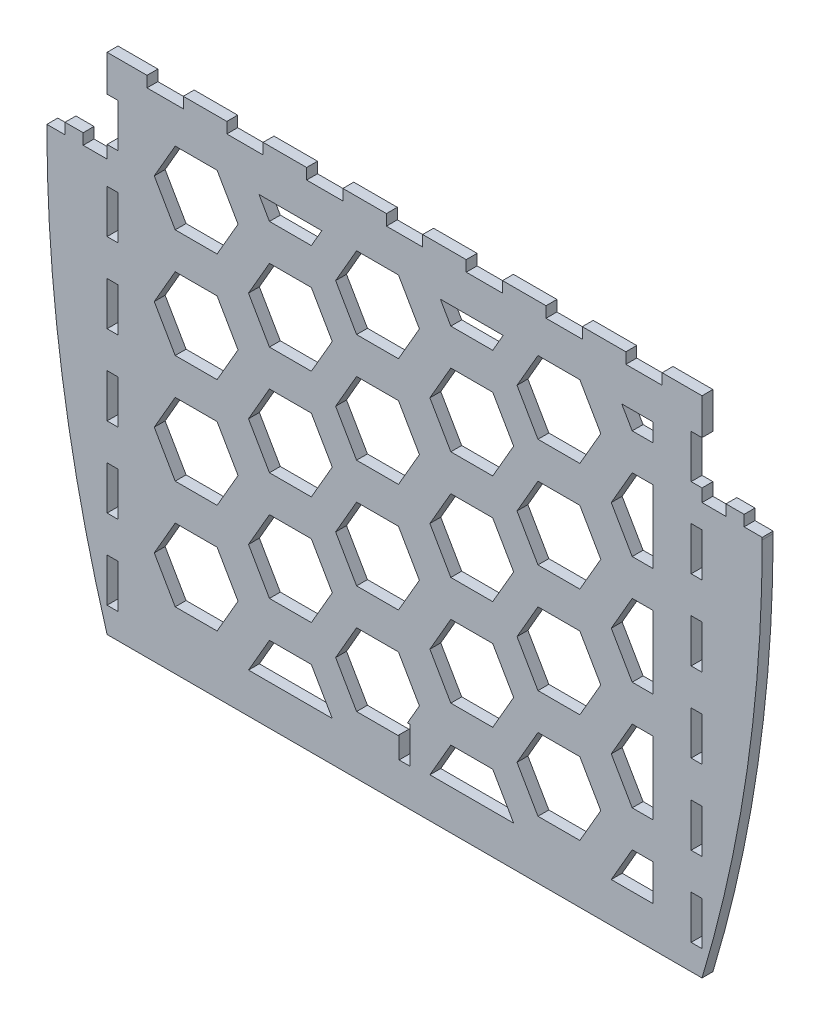
SolidWorks part; units mm, degrees
material "birch 3mm plywood"
ref_plane "Front Plane" through (0, 0, 0) normal (0, 0, 1) x (1, 0, 0)
ref_plane "Top Plane" through (0, 0, 0) normal (0, 1, 0) x (1, 0, 0)
ref_plane "Right Plane" through (0, 0, 0) normal (1, 0, 0) x (0, 0, -1)
sketch "Sketch1" plane through (0, 0, 152) normal (0, 0, 1) x (1, 0, 0)
  line L1 (-82, 69.5) -> (82, 69.5)
  line L2 (-82, 69.5) -> (-82, 44)
  line L3 (-82, -69.5) -> (82, -69.5)
  line L4 (82, 69.5) -> (82, 44)
  line L8 (-88.6, 47) -> (-93.6, 47)
  line L9 (-98.6, 44) -> (-98.6, 43.3771)
  line L12 (75, -62.5) -> (-75, -62.5) construction
  line L13 (75, 62.5) -> (75, -62.5) construction
  line L14 (-75, -62.5) -> (-75, 62.5) construction
  line L15 (-75, 62.5) -> (75, 62.5) construction
  line L33 (-93.6, 47) -> (-93.6, 44)
  line L34 (-93.6, 44) -> (-98.6, 44)
  line L35 (-88.6, 47) -> (-88.6, 44)
  line L36 (-88.6, 44) -> (-82, 44)
  line L37 (98.6, 44) -> (98.6, 43.3771)
  line L38 (93.6, 44) -> (98.6, 44)
  line L39 (93.6, 47) -> (93.6, 44)
  line L40 (88.6, 47) -> (93.6, 47)
  line L41 (88.6, 47) -> (88.6, 44)
  line L42 (88.6, 44) -> (82, 44)
  arc A12 (-98.6, 43.3771) -> (-82, -69.5) centre (293.4723, 43.3771) ccw
  arc A14 (98.6, 43.3771) -> (82, -69.5) centre (-293.4723, 43.3771) cw
  dimension "D3" = 7
  dimension "D11" = 150
  dimension "D12" = 125
  dimension "D13" = 7
  dimension "D14" = 22.5
  dimension "D15" = 16.6
  dimension "D16" = 3
  dimension "D17" = 5
  dimension "D18" = 5
extrude "Boss-Extrude1" add sketch "Sketch1" along normal blind 3
sketch "Sketch2" plane through (0, 0, 155) normal (0, 0, 1) x (1, 0, 0)
  line L0 (0, 69.5) -> (0, -69.5) construction
  line L1 (17, 69.5) -> (17, 66.5)
  line L2 (-5, 69.5) -> (5, 69.5)
  line L3 (-5, 69.5) -> (-5, 66.5)
  line L4 (-82, 69.5) -> (-82, 44)
  line L5 (-82, -69.5) -> (82, -69.5)
  line L6 (82, 44) -> (82, 69.5)
  line L7 (82, 69.5) -> (-82, 69.5)
  line L8 (-82, 69.5) -> (-82, 44)
  line L9 (-82, -69.5) -> (82, -69.5)
  line L10 (82, 44) -> (82, 69.5)
  line L11 (82, 69.5) -> (-82, 69.5)
  line L12 (-5, 66.5) -> (5, 66.5)
  line L13 (5, 69.5) -> (5, 66.5)
  line L14 (17, 69.5) -> (27, 69.5)
  line L15 (27, 69.5) -> (27, 66.5)
  line L16 (17, 66.5) -> (27, 66.5)
  line L17 (39, 69.5) -> (39, 66.5)
  line L18 (39, 69.5) -> (49, 69.5)
  line L19 (49, 69.5) -> (49, 66.5)
  line L20 (39, 66.5) -> (49, 66.5)
  line L21 (61, 69.5) -> (61, 66.5)
  line L22 (61, 69.5) -> (71, 69.5)
  line L23 (71, 69.5) -> (71, 66.5)
  line L24 (61, 66.5) -> (71, 66.5)
  line L25 (-27, 69.5) -> (-27, 66.5)
  line L26 (-27, 69.5) -> (-17, 69.5)
  line L27 (-17, 69.5) -> (-17, 66.5)
  line L28 (-27, 66.5) -> (-17, 66.5)
  line L29 (-49, 69.5) -> (-49, 66.5)
  line L30 (-49, 69.5) -> (-39, 69.5)
  line L31 (-39, 69.5) -> (-39, 66.5)
  line L32 (-49, 66.5) -> (-39, 66.5)
  line L33 (-71, 69.5) -> (-71, 66.5)
  line L34 (-71, 69.5) -> (-61, 69.5)
  line L35 (-61, 69.5) -> (-61, 66.5)
  line L36 (-71, 66.5) -> (-61, 66.5)
  line L37 (-82, 37.5) -> (-82, 25.5)
  line L38 (-82, 59.5) -> (-79, 59.5)
  line L39 (-82, 59.5) -> (-82, 47.5)
  line L40 (-82, 47.5) -> (-79, 47.5)
  line L41 (-79, 59.5) -> (-79, 47.5)
  line L42 (-82, 37.5) -> (-79, 37.5)
  line L43 (-79, 37.5) -> (-79, 25.5)
  line L44 (-82, 25.5) -> (-79, 25.5)
  line L45 (-82, 15.5) -> (-82, 3.5)
  line L46 (-82, 15.5) -> (-79, 15.5)
  line L47 (-79, 15.5) -> (-79, 3.5)
  line L48 (-82, 3.5) -> (-79, 3.5)
  line L49 (-82, -6.5) -> (-82, -18.5)
  line L50 (-82, -6.5) -> (-79, -6.5)
  line L51 (-79, -6.5) -> (-79, -18.5)
  line L52 (-82, -18.5) -> (-79, -18.5)
  line L53 (-82, -28.5) -> (-82, -40.5)
  line L54 (-82, -28.5) -> (-79, -28.5)
  line L55 (-79, -28.5) -> (-79, -40.5)
  line L56 (-82, -40.5) -> (-79, -40.5)
  line L57 (-82, -50.5) -> (-82, -62.5)
  line L58 (-82, -50.5) -> (-79, -50.5)
  line L59 (-79, -50.5) -> (-79, -62.5)
  line L60 (-82, -62.5) -> (-79, -62.5)
  line L65 (82, -50.5) -> (79, -50.5)
  line L66 (79, -50.5) -> (79, -62.5)
  line L67 (82, -62.5) -> (79, -62.5)
  line L68 (82, -50.5) -> (82, -62.5)
  line L69 (82, -28.5) -> (79, -28.5)
  line L70 (79, -28.5) -> (79, -40.5)
  line L71 (82, -40.5) -> (79, -40.5)
  line L72 (82, -28.5) -> (82, -40.5)
  line L73 (82, -6.5) -> (79, -6.5)
  line L74 (79, -6.5) -> (79, -18.5)
  line L75 (82, -18.5) -> (79, -18.5)
  line L76 (82, -6.5) -> (82, -18.5)
  line L77 (82, 15.5) -> (79, 15.5)
  line L78 (79, 15.5) -> (79, 3.5)
  line L79 (82, 3.5) -> (79, 3.5)
  line L80 (82, 15.5) -> (82, 3.5)
  line L81 (82, 37.5) -> (79, 37.5)
  line L82 (79, 37.5) -> (79, 25.5)
  line L83 (82, 25.5) -> (79, 25.5)
  line L84 (82, 37.5) -> (82, 25.5)
  line L85 (82, 47.5) -> (79, 47.5)
  line L86 (79, 59.5) -> (79, 47.5)
  line L87 (82, 59.5) -> (79, 59.5)
  line L88 (82, 59.5) -> (82, 47.5)
  line L97 (-88.6, 47) -> (-93.6, 47)
  line L98 (-88.6, 47) -> (-93.6, 47)
  line L99 (-98.6, 44) -> (-98.6, 43.3771)
  line L100 (-98.6, 44) -> (-98.6, 43.3771)
  line L101 (98.6, 43.3771) -> (98.6, 44)
  line L103 (98.6, 43.3771) -> (98.6, 44)
  line L109 (-82, 44) -> (-88.6, 44)
  line L110 (-82, 44) -> (-88.6, 44)
  line L111 (-88.6, 44) -> (-88.6, 47)
  line L112 (-88.6, 44) -> (-88.6, 47)
  line L113 (-93.6, 47) -> (-93.6, 44)
  line L114 (-93.6, 47) -> (-93.6, 44)
  line L115 (-93.6, 44) -> (-98.6, 44)
  line L116 (-93.6, 44) -> (-98.6, 44)
  line L121 (98.6, 44) -> (93.6, 44)
  line L122 (98.6, 44) -> (93.6, 44)
  line L123 (93.6, 44) -> (93.6, 47)
  line L124 (93.6, 44) -> (93.6, 47)
  line L125 (93.6, 47) -> (88.6, 47)
  line L126 (93.6, 47) -> (88.6, 47)
  line L127 (88.6, 47) -> (88.6, 44)
  line L128 (88.6, 47) -> (88.6, 44)
  line L129 (88.6, 44) -> (82, 44)
  line L130 (88.6, 44) -> (82, 44)
  arc A2 (-98.6, 43.3771) -> (-82, -69.5) centre (293.4723, 43.3771) ccw
  arc A3 (-98.6, 43.3771) -> (-82, -69.5) centre (293.4723, 43.3771) ccw
  arc A4 (82, -69.5) -> (98.6, 43.3771) centre (-293.4723, 43.3771) ccw
  arc A6 (82, -69.5) -> (98.6, 43.3771) centre (-293.4723, 43.3771) ccw
  point P10 (0, 66.5)
  line M64 (82, 44) -> (82, 69.5)
  line M65 (82, 69.5) -> (-82, 69.5)
  dimension "D2" = 10
  dimension "D3" = 3
  dimension "D6" = 12
  dimension "D7" = 12
  dimension "D8" = 3
  dimension "D9" = 12
  dimension "D10" = 10
  dimension "D12" = 10
  dimension "D1" = 0
  dimension "D4" = 4
  dimension "D5" = 4
  dimension "D11" = 6
extrude "Cut-Extrude1" cut sketch "Sketch2" against normal blind 10 contours L8 L44 L43 L42 | L33 L36 L35 L11 | L29 L32 L31 M65 | L25 L28 L27 L11 | L0 L12 L13 M65 | L0 L11 L3 L12 | L1 L16 L15 L11 | L17 L20 L19 L11 | L21 L24 L23 L11 | L87 L86 L85 M64 | L79 L77 L78 M64 | L75 L10 L73 L74 | L71 L69 L70 M64 | L67 L10 L65 L66 | L41 L40 L39 L38 | L47 L48 L45 L46 | L51 L52 L49 L50 | L55 L56 L53 L54 | L59 L60 L57 L58 | L82 L83 L84 L81 region at (2.5, 68, 155) region at (-2.5, 68, 155) region at (-22, 68, 155) region at (22, 68, 155) region at (-44, 68, 155) region at (44, 68, 155) region at (-66, 68, 155) region at (66, 68, 155) region at (80.5, 53.5, 155) region at (-80.5, 31.5, 155) region at (80.5, -56.5, 155) region at (80.5, -34.5, 155) region at (80.5, -12.5, 155) region at (80.5, 9.5, 155)
sketch "Sketch3" plane through (0, 0, 155) normal (0, 0, 1) x (1, 0, 0)
  line L0 (-49, 66.5) -> (-39, 66.5) construction
  line L1 (-45.906, 46.5) -> (-51.6795, 56.5)
  line L2 (-51.6795, 56.5) -> (-63.2265, 56.5)
  line L3 (-63.2265, 56.5) -> (-69, 46.5)
  line L4 (-69, 46.5) -> (-63.2265, 36.5)
  line L5 (-63.2265, 36.5) -> (-51.6795, 36.5)
  line L6 (-51.6795, 36.5) -> (-45.906, 46.5)
  line L7 (-79, 37.5) -> (-79, 25.5) construction
  line L8 (-19.9252, 31.5) -> (-25.6987, 41.5)
  line L9 (-25.6987, 41.5) -> (-37.2457, 41.5)
  line L10 (-37.2457, 41.5) -> (-43.0192, 31.5)
  line L11 (-43.0192, 31.5) -> (-37.2457, 21.5)
  line L12 (-37.2457, 21.5) -> (-25.6987, 21.5)
  line L13 (-25.6987, 21.5) -> (-19.9252, 31.5)
  line L14 (4.094, 46.5) -> (-1.6795, 56.5)
  line L15 (-1.6795, 56.5) -> (-13.2265, 56.5)
  line L16 (-13.2265, 56.5) -> (-19, 46.5)
  line L17 (-19, 46.5) -> (-13.2265, 36.5)
  line L18 (-13.2265, 36.5) -> (-1.6795, 36.5)
  line L19 (-1.6795, 36.5) -> (4.094, 46.5)
  line L20 (30.0748, 31.5) -> (24.3013, 41.5)
  line L21 (24.3013, 41.5) -> (12.7543, 41.5)
  line L22 (12.7543, 41.5) -> (6.9808, 31.5)
  line L23 (6.9808, 31.5) -> (12.7543, 21.5)
  line L24 (12.7543, 21.5) -> (24.3013, 21.5)
  line L25 (24.3013, 21.5) -> (30.0748, 31.5)
  line L26 (54.094, 46.5) -> (48.3205, 56.5)
  line L27 (48.3205, 56.5) -> (36.7735, 56.5)
  line L28 (36.7735, 56.5) -> (31, 46.5)
  line L29 (31, 46.5) -> (36.7735, 36.5)
  line L30 (36.7735, 36.5) -> (48.3205, 36.5)
  line L31 (48.3205, 36.5) -> (54.094, 46.5)
  line L33 (68.5278, 41.5) -> (62.7543, 41.5)
  line L34 (62.7543, 41.5) -> (56.9808, 31.5)
  line L35 (56.9808, 31.5) -> (62.7543, 21.5)
  line L36 (62.7543, 21.5) -> (68.5278, 21.5)
  line L38 (4.094, 16.5) -> (-1.6795, 26.5)
  line L39 (-1.6795, 26.5) -> (-13.2265, 26.5)
  line L40 (-13.2265, 26.5) -> (-19, 16.5)
  line L41 (-19, 16.5) -> (-13.2265, 6.5)
  line L42 (-13.2265, 6.5) -> (-1.6795, 6.5)
  line L43 (-1.6795, 6.5) -> (4.094, 16.5)
  line L44 (30.0748, 1.5) -> (24.3013, 11.5)
  line L45 (24.3013, 11.5) -> (12.7543, 11.5)
  line L46 (12.7543, 11.5) -> (6.9808, 1.5)
  line L47 (6.9808, 1.5) -> (12.7543, -8.5)
  line L48 (12.7543, -8.5) -> (24.3013, -8.5)
  line L49 (24.3013, -8.5) -> (30.0748, 1.5)
  line L50 (54.094, 16.5) -> (48.3205, 26.5)
  line L51 (48.3205, 26.5) -> (36.7735, 26.5)
  line L52 (36.7735, 26.5) -> (31, 16.5)
  line L53 (31, 16.5) -> (36.7735, 6.5)
  line L54 (36.7735, 6.5) -> (48.3205, 6.5)
  line L55 (48.3205, 6.5) -> (54.094, 16.5)
  line L57 (68.5278, 11.5) -> (62.7543, 11.5)
  line L58 (62.7543, 11.5) -> (56.9808, 1.5)
  line L59 (56.9808, 1.5) -> (62.7543, -8.5)
  line L60 (62.7543, -8.5) -> (68.5278, -8.5)
  line L62 (4.094, -13.5) -> (-1.6795, -3.5)
  line L63 (-1.6795, -3.5) -> (-13.2265, -3.5)
  line L64 (-13.2265, -3.5) -> (-19, -13.5)
  line L65 (-19, -13.5) -> (-13.2265, -23.5)
  line L66 (-13.2265, -23.5) -> (-1.6795, -23.5)
  line L67 (-1.6795, -23.5) -> (4.094, -13.5)
  line L68 (30.0748, -28.5) -> (24.3013, -18.5)
  line L69 (24.3013, -18.5) -> (12.7543, -18.5)
  line L70 (12.7543, -18.5) -> (6.9808, -28.5)
  line L71 (6.9808, -28.5) -> (12.7543, -38.5)
  line L72 (12.7543, -38.5) -> (24.3013, -38.5)
  line L73 (24.3013, -38.5) -> (30.0748, -28.5)
  line L74 (54.094, -13.5) -> (48.3205, -3.5)
  line L75 (48.3205, -3.5) -> (36.7735, -3.5)
  line L76 (36.7735, -3.5) -> (31, -13.5)
  line L77 (31, -13.5) -> (36.7735, -23.5)
  line L78 (36.7735, -23.5) -> (48.3205, -23.5)
  line L79 (48.3205, -23.5) -> (54.094, -13.5)
  line L81 (68.5278, -18.5) -> (62.7543, -18.5)
  line L82 (62.7543, -18.5) -> (56.9808, -28.5)
  line L83 (56.9808, -28.5) -> (62.7543, -38.5)
  line L84 (62.7543, -38.5) -> (68.5278, -38.5)
  line L86 (4.094, -43.5) -> (-1.6795, -33.5)
  line L87 (-1.6795, -33.5) -> (-13.2265, -33.5)
  line L88 (-13.2265, -33.5) -> (-19, -43.5)
  line L89 (-19, -43.5) -> (-13.2265, -53.5)
  line L90 (-13.2265, -53.5) -> (-1.6795, -53.5)
  line L91 (-1.6795, -53.5) -> (4.094, -43.5)
  line L92 (30.0748, -58.5) -> (24.3013, -48.5)
  line L93 (24.3013, -48.5) -> (12.7543, -48.5)
  line L94 (12.7543, -48.5) -> (6.9808, -58.5)
  line L98 (54.094, -43.5) -> (48.3205, -33.5)
  line L99 (48.3205, -33.5) -> (36.7735, -33.5)
  line L100 (36.7735, -33.5) -> (31, -43.5)
  line L101 (31, -43.5) -> (36.7735, -53.5)
  line L102 (36.7735, -53.5) -> (48.3205, -53.5)
  line L103 (48.3205, -53.5) -> (54.094, -43.5)
  line L105 (68.5278, -48.5) -> (62.7543, -48.5)
  line L106 (62.7543, -48.5) -> (56.9808, -58.5)
  line L134 (-45.906, 16.5) -> (-51.6795, 26.5)
  line L135 (-51.6795, 26.5) -> (-63.2265, 26.5)
  line L136 (-63.2265, 26.5) -> (-69, 16.5)
  line L137 (-69, 16.5) -> (-63.2265, 6.5)
  line L138 (-63.2265, 6.5) -> (-51.6795, 6.5)
  line L139 (-51.6795, 6.5) -> (-45.906, 16.5)
  line L140 (-19.9252, 1.5) -> (-25.6987, 11.5)
  line L141 (-25.6987, 11.5) -> (-37.2457, 11.5)
  line L142 (-37.2457, 11.5) -> (-43.0192, 1.5)
  line L143 (-43.0192, 1.5) -> (-37.2457, -8.5)
  line L144 (-37.2457, -8.5) -> (-25.6987, -8.5)
  line L145 (-25.6987, -8.5) -> (-19.9252, 1.5)
  line L146 (-45.906, -13.5) -> (-51.6795, -3.5)
  line L147 (-51.6795, -3.5) -> (-63.2265, -3.5)
  line L148 (-63.2265, -3.5) -> (-69, -13.5)
  line L149 (-69, -13.5) -> (-63.2265, -23.5)
  line L150 (-63.2265, -23.5) -> (-51.6795, -23.5)
  line L151 (-51.6795, -23.5) -> (-45.906, -13.5)
  line L152 (-19.9252, -28.5) -> (-25.6987, -18.5)
  line L153 (-25.6987, -18.5) -> (-37.2457, -18.5)
  line L154 (-37.2457, -18.5) -> (-43.0192, -28.5)
  line L155 (-43.0192, -28.5) -> (-37.2457, -38.5)
  line L156 (-37.2457, -38.5) -> (-25.6987, -38.5)
  line L157 (-25.6987, -38.5) -> (-19.9252, -28.5)
  line L158 (-45.906, -43.5) -> (-51.6795, -33.5)
  line L159 (-51.6795, -33.5) -> (-63.2265, -33.5)
  line L160 (-63.2265, -33.5) -> (-69, -43.5)
  line L161 (-69, -43.5) -> (-63.2265, -53.5)
  line L162 (-63.2265, -53.5) -> (-51.6795, -53.5)
  line L163 (-51.6795, -53.5) -> (-45.906, -43.5)
  line L164 (-19.9252, -58.5) -> (-25.6987, -48.5)
  line L165 (-25.6987, -48.5) -> (-37.2457, -48.5)
  line L166 (-37.2457, -48.5) -> (-43.0192, -58.5)
  line L185 (-40.1325, 56.5) -> (-37.2457, 51.5)
  line L186 (-37.2457, 51.5) -> (-25.6987, 51.5)
  line L187 (-25.6987, 51.5) -> (-22.812, 56.5)
  line L188 (31, -73.5) -> (36.7735, -83.5) [skipped]
  line L189 (36.7735, -83.5) -> (48.3205, -83.5) [skipped]
  line L190 (48.3205, -83.5) -> (54.094, -73.5) [skipped]
  line L191 (80.0748, -88.5) -> (74.3013, -78.5) [skipped]
  line L192 (74.3013, -78.5) -> (62.7543, -78.5) [skipped]
  line L193 (62.7543, -78.5) -> (56.9808, -88.5) [skipped]
  line L194 (56.9808, -88.5) -> (62.7543, -98.5) [skipped]
  line L195 (62.7543, -98.5) -> (74.3013, -98.5) [skipped]
  line L196 (74.3013, -98.5) -> (80.0748, -88.5) [skipped]
  line L197 (54.094, -73.5) -> (48.3205, -63.5) [skipped]
  line L198 (48.3205, -63.5) -> (36.7735, -63.5) [skipped]
  line L199 (36.7735, -63.5) -> (31, -73.5) [skipped]
  line L200 (-1.6795, -83.5) -> (4.094, -73.5) [skipped]
  line L201 (30.0748, -88.5) -> (24.3013, -78.5) [skipped]
  line L202 (24.3013, -78.5) -> (12.7543, -78.5) [skipped]
  line L203 (12.7543, -78.5) -> (6.9808, -88.5) [skipped]
  line L204 (6.9808, -88.5) -> (12.7543, -98.5) [skipped]
  line L205 (12.7543, -98.5) -> (24.3013, -98.5) [skipped]
  line L206 (24.3013, -98.5) -> (30.0748, -88.5) [skipped]
  line L207 (4.094, -73.5) -> (-1.6795, -63.5) [skipped]
  line L208 (-1.6795, -63.5) -> (-13.2265, -63.5) [skipped]
  line L209 (-13.2265, -63.5) -> (-19, -73.5) [skipped]
  line L210 (-19, -73.5) -> (-13.2265, -83.5) [skipped]
  line L211 (-13.2265, -83.5) -> (-1.6795, -83.5) [skipped]
  line L212 (-19.9252, -88.5) -> (-25.6987, -78.5) [skipped]
  line L213 (-25.6987, -78.5) -> (-37.2457, -78.5) [skipped]
  line L214 (-37.2457, -78.5) -> (-43.0192, -88.5) [skipped]
  line L215 (-43.0192, -88.5) -> (-37.2457, -98.5) [skipped]
  line L216 (-37.2457, -98.5) -> (-25.6987, -98.5) [skipped]
  line L217 (-25.6987, -98.5) -> (-19.9252, -88.5) [skipped]
  line L218 (-45.906, -73.5) -> (-51.6795, -63.5) [skipped]
  line L219 (-51.6795, -63.5) -> (-63.2265, -63.5) [skipped]
  line L220 (-63.2265, -63.5) -> (-69, -73.5) [skipped]
  line L221 (-69, -73.5) -> (-63.2265, -83.5) [skipped]
  line L222 (-63.2265, -83.5) -> (-51.6795, -83.5) [skipped]
  line L223 (-51.6795, -83.5) -> (-45.906, -73.5) [skipped]
  line L224 (-40.1325, 56.5) -> (-22.812, 56.5)
  line L225 (24.3013, 51.5) -> (27.188, 56.5)
  line L226 (-25.6987, 71.5) -> (-37.2457, 71.5) [skipped]
  line L227 (-19.9252, 61.5) -> (-25.6987, 71.5) [skipped]
  line L228 (-37.2457, 71.5) -> (-43.0192, 61.5) [skipped]
  line L229 (9.8675, 56.5) -> (27.188, 56.5)
  line L230 (12.7543, 51.5) -> (24.3013, 51.5)
  line L231 (9.8675, 56.5) -> (12.7543, 51.5)
  line L233 (59.8675, 56.5) -> (68.5278, 56.5)
  line L234 (62.7543, 51.5) -> (68.5278, 51.5)
  line L235 (59.8675, 56.5) -> (62.7543, 51.5)
  line L236 (68.5278, 56.5) -> (68.5278, 51.5)
  line L237 (68.5278, 41.5) -> (68.5278, 21.5)
  line L238 (68.5278, 11.5) -> (68.5278, -8.5)
  line L239 (68.5278, -18.5) -> (68.5278, -38.5)
  line L240 (68.5278, -48.5) -> (68.5278, -58.5)
  line L241 (56.9808, -58.5) -> (68.5278, -58.5)
  line L242 (6.9808, -58.5) -> (30.0748, -58.5)
  line L243 (-43.0192, -58.5) -> (-19.9252, -58.5)
  line L245 (74.3013, 51.5) -> (77.188, 56.5) [skipped]
  line L246 (80.0748, -58.5) -> (74.3013, -48.5) [skipped]
  line L247 (74.3013, -68.5) -> (80.0748, -58.5) [skipped]
  line L248 (62.7543, -68.5) -> (74.3013, -68.5) [skipped]
  line L249 (56.9808, -58.5) -> (62.7543, -68.5) [skipped]
  line L250 (74.3013, -38.5) -> (80.0748, -28.5) [skipped]
  line L251 (80.0748, -28.5) -> (74.3013, -18.5) [skipped]
  line L252 (74.3013, -8.5) -> (80.0748, 1.5) [skipped]
  line L253 (80.0748, 1.5) -> (74.3013, 11.5) [skipped]
  line L254 (80.0748, 31.5) -> (74.3013, 41.5) [skipped]
  line L255 (74.3013, 21.5) -> (80.0748, 31.5) [skipped]
  line L256 (6.9808, -58.5) -> (12.7543, -68.5) [skipped]
  line L257 (12.7543, -68.5) -> (24.3013, -68.5) [skipped]
  line L258 (24.3013, -68.5) -> (30.0748, -58.5) [skipped]
  line L259 (-25.6987, -68.5) -> (-19.9252, -58.5) [skipped]
  line L260 (-43.0192, -58.5) -> (-37.2457, -68.5) [skipped]
  line L261 (-37.2457, -68.5) -> (-25.6987, -68.5) [skipped]
  circle A0 centre (-57.453, 46.5) radius 10 construction
  circle A1 centre (-31.4722, 31.5) radius 10 construction
  circle A2 centre (-7.453, 46.5) radius 10 construction
  circle A3 centre (18.5278, 31.5) radius 10 construction
  circle A4 centre (42.547, 46.5) radius 10 construction
  circle A5 centre (68.5278, 31.5) radius 10 construction
  circle A6 centre (-7.453, 16.5) radius 10 construction
  circle A7 centre (18.5278, 1.5) radius 10 construction
  circle A8 centre (42.547, 16.5) radius 10 construction
  circle A9 centre (68.5278, 1.5) radius 10 construction
  circle A10 centre (-7.453, -13.5) radius 10 construction
  circle A11 centre (18.5278, -28.5) radius 10 construction
  circle A12 centre (42.547, -13.5) radius 10 construction
  circle A13 centre (68.5278, -28.5) radius 10 construction
  circle A14 centre (-7.453, -43.5) radius 10 construction
  circle A15 centre (18.5278, -58.5) radius 10 construction
  circle A16 centre (42.547, -43.5) radius 10 construction
  circle A17 centre (68.5278, -58.5) radius 10 construction
  circle A18 centre (18.5278, 61.5) radius 10 construction
  circle A19 centre (68.5278, 61.5) radius 10 construction
  circle A22 centre (-57.453, 16.5) radius 10 construction
  circle A23 centre (-31.4722, 1.5) radius 10 construction
  circle A24 centre (-57.453, -13.5) radius 10 construction
  circle A25 centre (-31.4722, -28.5) radius 10 construction
  circle A26 centre (-57.453, -43.5) radius 10 construction
  circle A27 centre (-31.4722, -58.5) radius 10 construction
  circle A30 centre (-31.4722, 61.5) radius 10 construction
  circle A31 centre (42.547, -73.5) radius 10 construction
  circle A32 centre (68.5278, -88.5) radius 10 construction
  circle A33 centre (-7.453, -73.5) radius 10 construction
  circle A34 centre (18.5278, -88.5) radius 10 construction
  circle A35 centre (-31.4722, -88.5) radius 10 construction
  circle A36 centre (-57.453, -73.5) radius 10 construction
  dimension "D3" = 20
  dimension "D1" = 10
  dimension "D2" = 10
  dimension "D4" = 2
  dimension "D5" = 3
  dimension "D6" = 5
  dimension "D7" = 2
  dimension "D8" = 3
extrude "Cut-Extrude2" cut sketch "Sketch3" against normal through all
sketch "Sketch4" plane through (0, 0, 155) normal (0, 0, 1) x (1, 0, 0)
  line L4 (-1.5, -59.5) -> (-1.5, -64.5)
  line L5 (1.5, -59.5) -> (-1.5, -59.5)
  line L6 (1.5, -64.5) -> (1.5, -59.5)
  line L7 (-1.5, -64.5) -> (1.5, -64.5)
  line L8 (-1.5, -59.5) -> (-1.5, -64.5)
  line L9 (1.5, -59.5) -> (-1.5, -59.5)
  line L10 (1.5, -64.5) -> (1.5, -59.5)
  line L11 (-1.5, -64.5) -> (1.5, -64.5)
  circle A0 centre (22.8668, -34.5) radius 1.7 construction
  circle A1 centre (22.8668, -57.9) radius 1.7 construction
  circle A2 centre (22.8668, -34.5) radius 1.7
  circle A3 centre (22.8668, -57.9) radius 1.7
  dimension "D1" = 0
sketch "Sketch5" plane through (0, 0, 155) normal (0, 0, 1) x (1, 0, 0)
  line L4 (-1.5, -49.1933) -> (-1.5, -59.1933)
  line L5 (-1.5, -59.1933) -> (1.5, -59.1933)
  line L6 (1.5, -59.1933) -> (1.5, -49.1933)
  line L7 (1.5, -49.1933) -> (-1.5, -49.1933)
  line L8 (-1.5, -49.1933) -> (-1.5, -59.1933)
  line L9 (-1.5, -59.1933) -> (1.5, -59.1933)
  line L10 (1.5, -59.1933) -> (1.5, -49.1933)
  line L11 (1.5, -49.1933) -> (-1.5, -49.1933)
  dimension "D1" = 0
extrude "Cut-Extrude3" cut sketch "Sketch5" against normal blind 10
